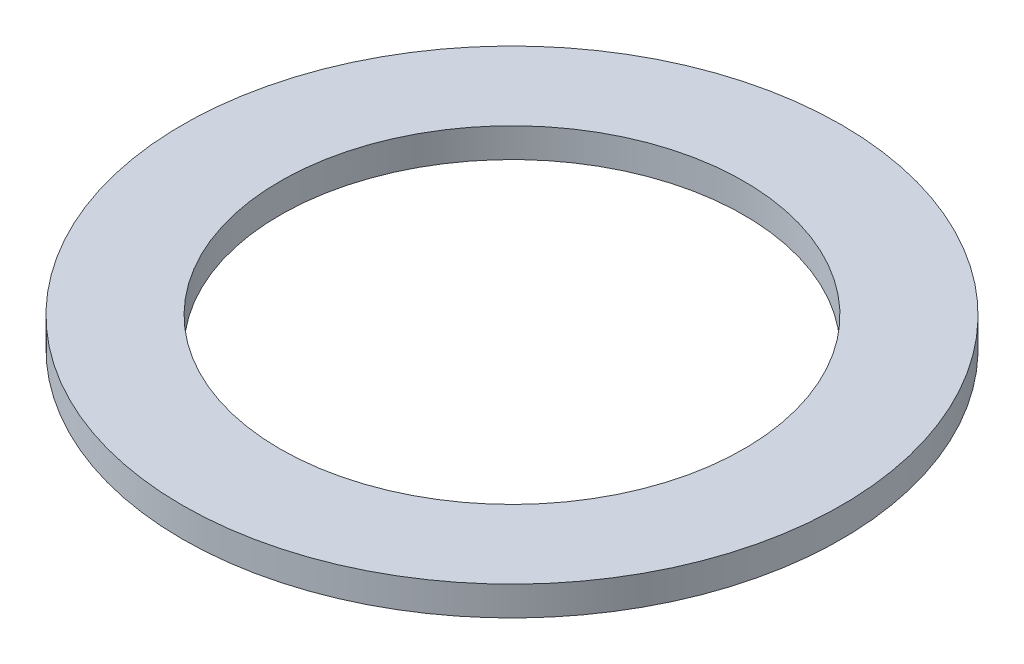
SolidWorks part; units mm, degrees
ref_plane "Front Plane" through (0, 0, 0) normal (0, 0, 1) x (1, 0, 0)
ref_plane "Top Plane" through (0, 0, 0) normal (0, 1, 0) x (1, 0, 0)
ref_plane "Right Plane" through (0, 0, 0) normal (1, 0, 0) x (0, 0, -1)
sketch "Sketch1" plane through (0, 0, 0) normal (0, 1, 0) x (1, 0, 0)
  circle A0 centre (0, 0) radius 67.5
  dimension "FLANGE_OD" = 135
extrude "Boss-Extrude1" add sketch "Sketch1" along normal blind 6
sketch "Sketch2" plane through (0, 0, 0) normal (0, 1, 0) x (1, 0, 0)
  circle A0 centre (0, 0) radius 47.5
  dimension "BORE_D" = 95
extrude "Cut-Extrude1" cut sketch "Sketch2" along normal through all
sketch "Sketch3" plane through (0, 6, 0) normal (0, 1, 0) x (1, 0, 0)
  circle A0 centre (0, 0) radius 26.6533 construction
  circle A1 centre (-26.6533, 0) radius 2.5186
  dimension "BOLT_D" = 5.0371
  dimension "BOLT_PCD" = 53.3066
extrude "Cut-Extrude2" cut sketch "Sketch3" against normal blind 3.8933 rebuild error yes
pattern_circular "CirPattern1" count 4 over 360 rebuild error yes
